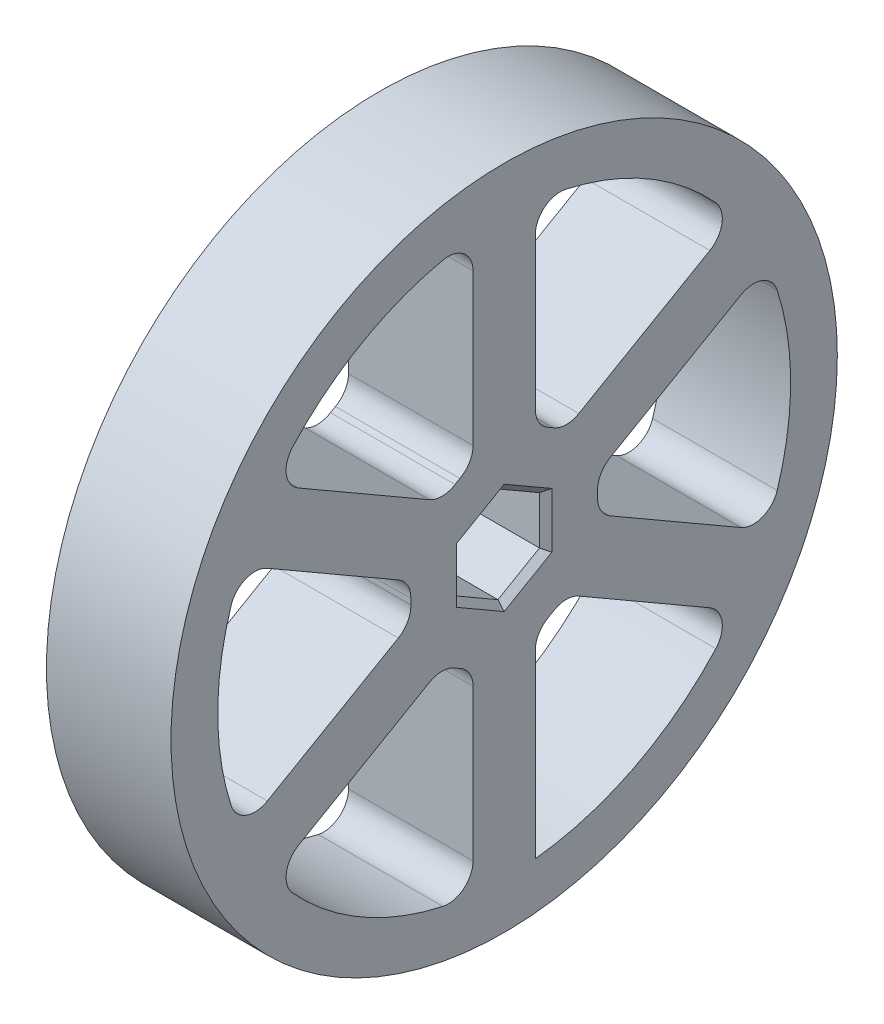
SolidWorks part; units mm, degrees
ref_plane "Front Plane" through (0, 0, 0) normal (0, 0, 1) x (1, 0, 0)
ref_plane "Top Plane" through (0, 0, 0) normal (0, 1, 0) x (1, 0, 0)
ref_plane "Right Plane" through (0, 0, 0) normal (1, 0, 0) x (0, 0, -1)
sketch "Axle Profile" plane through (0, 0, 0) normal (1, 0, 0) x (0, 0, -1)
  line L1 (0, -4.8895) -> (4.2344, -2.4448)
  line L2 (4.2344, -2.4448) -> (4.2344, 2.4447)
  line L3 (4.2344, 2.4447) -> (0, 4.8895)
  line L4 (0, 4.8895) -> (-4.2344, 2.4448)
  line L5 (-4.2344, 2.4448) -> (-4.2344, -2.4448)
  line L6 (-4.2344, -2.4448) -> (0, -4.8895)
  circle A0 centre (0, 0) radius 4.8895 construction
  circle A1 centre (0, 0) radius 9.525
  dimension "D1" = 9.779
  dimension ".625" = 19.05
extrude "Wheel Hub" add sketch "Axle Profile" along normal blind 12.7
fillet "Hub Fillet" [suppressed] radius 2.032
ref_plane "Spoke Plane" through (0, 0, -4.2344) normal (0, 0, 1) x (1, 0, 0)
sketch "Sketch2" plane through (0, 0, -4.2344) normal (0, 0, 1) x (1, 0, 0)
  line L0 (12.7, 2.4448) -> (0, -2.4447) construction
  line L1 (0, 2.4448) -> (12.7, -2.4447) construction
  circle A0 centre (6.35, 0) radius 2.54
  dimension "D1" = 5.08
extrude "Spoke" [suppressed] add sketch "Sketch2" against normal blind 25.4
ref_axis "Pattern Axis" through (12.7, 0, 0) along (-1, 0, 0)
pattern_circular "CirPattern1" [suppressed] count 6 over 360 about axis through (12.7, 0, 0) along (-1, 0, 0) of bodies 102
fillet "Hub/Spoke Fillet" [suppressed] radius 2.54
ref_plane "Mid Plane" through (6.35, 0, 0) normal (-1, 0, 0) x (0, 0, 1)
sketch "Sketch3" plane through (6.35, 0, 0) normal (-1, 0, 0) x (0, 0, 1)
  circle A0 centre (0, 0) radius 29.21
  circle A1 centre (0, 0) radius 33.9725
  dimension "D1" = 58.42
  dimension "D2" = 67.945
extrude "Wheel Rim" add sketch "Sketch3" along normal up to surface and the other way up to surface up to face at (0, 0, -9.525) other way up to face at (12.7, 0, -9.525)
fillet "Rim/Spoke Fillet" [suppressed] radius 2.54
fillet "Rim Fillet" [suppressed] radius 0.762
sketch "Sketch4" plane through (12.7, 0, 0) normal (1, 0, 0) x (0, 0, -1)
  line L0 (0, 8.9803) -> (0, 0) construction
  line L1 (-3.175, 8.9803) -> (3.175, 8.9803)
  line L2 (-3.175, 8.9803) -> (-3.175, 29.21)
  line L3 (-3.175, 29.21) -> (3.175, 29.21)
  line L4 (3.175, 8.9803) -> (3.175, 29.21)
  circle A0 centre (0, 0) radius 9.525 construction
  circle A1 centre (0, 0) radius 29.21 construction
  point P8 (0, 0)
  dimension "D1" = 6.35
extrude "Boss-Extrude1" add sketch "Sketch4" against normal up to surface (12.7 mm away) up to face at (0, 0, -29.21)
pattern_circular "Spokes" count 6 over 360 about axis through (0, 0, 0) along (1, 0, 0) of "Boss-Extrude1"
fillet "Spoke Fillets" radius 2.54 23 edges at (6.35, 8.9803, 3.175) (6.35, 7.2398, 6.1896) (6.35, -1.7405, 9.3646) (6.35, 1.7405, 9.3646) (6.35, -8.9803, 3.175) (6.35, -7.2398, 6.1896) (6.35, -8.9803, -3.175) (6.35, -7.2398, -6.1896) (6.35, -1.7405, -9.3646) (6.35, 1.7405, -9.3646) (6.35, 7.2398, -6.1896) (6.35, 8.9803, -3.175) (6.35, 29.0369, -3.175) (6.35, 29.0369, 3.175) (6.35, 17.2681, 23.5592) (6.35, 11.7688, 26.7342) (6.35, -11.7688, 26.7342) (6.35, -17.2681, 23.5592) (6.35, -29.0369, 3.175) (6.35, -17.2681, -23.5592) (6.35, -11.7688, -26.7342) (6.35, 11.7688, -26.7342) (6.35, 17.2681, -23.5592)
chamfer "Shaft Chamfers" distance 0.635 angle 45 12 edges at (0, 0, 4.2344) (0, 3.6671, 2.1172) (0, 3.6671, -2.1172) (0, 0, -4.2344) (0, -3.6671, -2.1172) (0, -3.6671, 2.1172) (12.7, -3.6671, -2.1172) (12.7, -3.6671, 2.1172) (12.7, 0, 4.2344) (12.7, 3.6671, 2.1172) (12.7, 3.6671, -2.1172) (12.7, 0, -4.2344)
